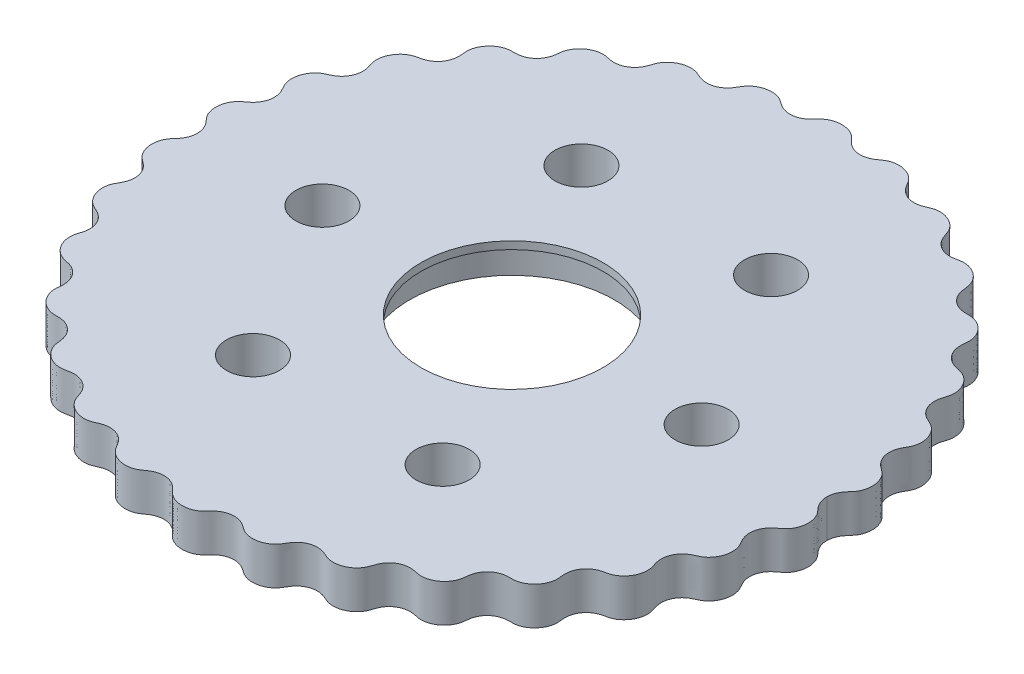
SolidWorks part; units mm, degrees
ref_plane "Front Plane" through (0, 0, 0) normal (0, 0, 1) x (1, 0, 0)
ref_plane "Top Plane" through (0, 0, 0) normal (0, 1, 0) x (1, 0, 0)
ref_plane "Right Plane" through (0, 0, 0) normal (1, 0, 0) x (0, 0, -1)
sketch "Sketch1" plane through (0, 0, 0) normal (0, 1, 0) x (1, 0, 0)
  circle A0 centre (1, 0) radius 13.5
  circle A1 centre (26, 0) radius 3.5
  circle A2 centre (13.5, 21.6506) radius 3.5
  circle A3 centre (-11.5, 21.6506) radius 3.5
  circle A4 centre (-24, 0) radius 3.5
  circle A5 centre (-11.5, -21.6506) radius 3.5
  circle A6 centre (13.5, -21.6506) radius 3.5
  spline S0 degree 3 number of poles 1508 (-40.5029, 0.0721) -> (42.5, 0)
  spline S1 degree 3 number of poles 1509 (42.5, 0) -> (-40.5029, 0.0721)
  point P0 (0, 0)
extrude "Boss-Extrude1" add sketch "Sketch1" along normal blind 5
sketch "Sketch2" plane through (0, 5, 0) normal (0, 1, 0) x (1, 0, 0)
  circle A0 centre (1, 0) radius 13.5
  circle A1 centre (1, 0) radius 12
  dimension "D1" = 24
extrude "Boss-Extrude2" add sketch "Sketch2" against normal blind 1
